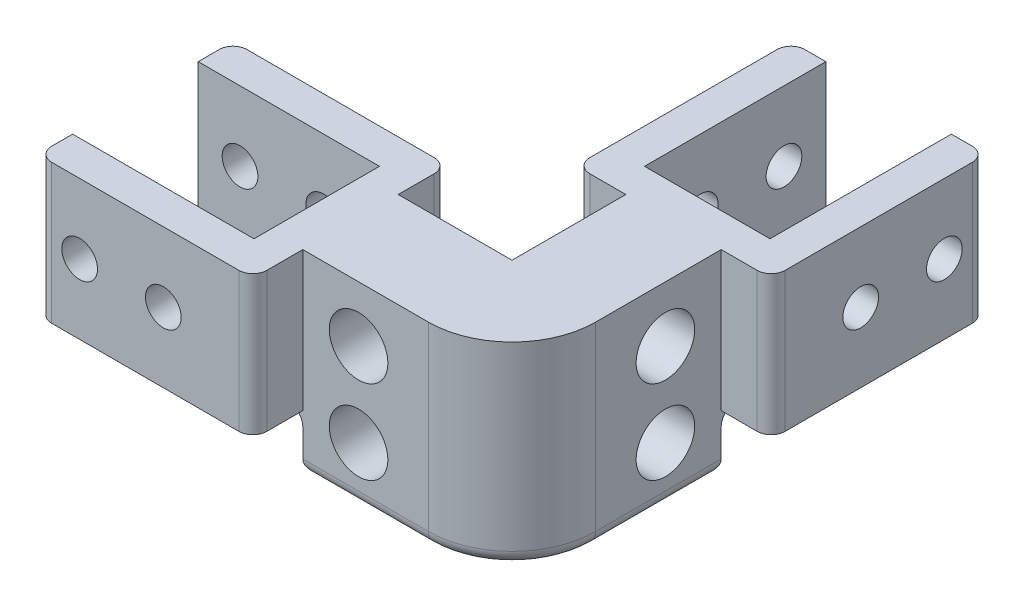
SolidWorks part; units mm, degrees
ref_plane "정면" through (0, 0, 0) normal (0, 0, 1) x (1, 0, 0)
ref_plane "윗면" through (0, 0, 0) normal (0, 1, 0) x (1, 0, 0)
ref_plane "우측면" through (0, 0, 0) normal (1, 0, 0) x (0, 0, -1)
sketch "스케치1" plane through (0, 0, 0) normal (0, 1, 0) x (1, 0, 0)
  line L0 (-17.5, 67.5) -> (-11.25, 67.5)
  line L1 (-11.25, 67.5) -> (-11.25, 37.5)
  line L2 (-11.25, 37.5) -> (11.25, 37.5)
  line L3 (11.25, 37.5) -> (11.25, 67.5)
  line L4 (11.25, 67.5) -> (17.5, 67.5)
  line L5 (17.5, 67.5) -> (17.5, -17.5)
  line L6 (17.5, -17.5) -> (-67.5, -17.5)
  line L7 (-67.5, -17.5) -> (-67.5, -11.25)
  line L8 (-67.5, -11.25) -> (-37.5, -11.25)
  line L9 (-37.5, -11.25) -> (-37.5, 11.25)
  line L10 (-37.5, 11.25) -> (-67.5, 11.25)
  line L11 (-67.5, 11.25) -> (-67.5, 17.5)
  line L12 (-67.5, 17.5) -> (-17.5, 17.5)
  line L13 (-17.5, 17.5) -> (-17.5, 67.5)
  point P14 (0, 37.5)
  point P18 (-37.5, 0)
  point P21 (-67.5, -14.375)
  dimension "D1" = 22.5
  dimension "D2" = 22.5
  dimension "D3" = 35
  dimension "D4" = 35
  dimension "D5" = 30
  dimension "D6" = 30
  dimension "D7" = 37.5
  dimension "D8" = 37.5
extrude "보스-돌출1" add sketch "스케치1" along normal blind 25
sketch "스케치2" plane through (17.5, 0, 0) normal (1, 0, 0) x (0, 0, -1)
  line L0 (67.5, 25) -> (67.5, 0) construction
  line L1 (-17.5, 25) -> (67.5, 25) construction
  circle A0 centre (60, 12.5) radius 3.2
  circle A1 centre (45, 12.5) radius 3.2
  dimension "D3" = 6.4
  dimension "D1" = 15
  dimension "D2" = 7.5
  dimension "D4" = 12.5
extrude "컷-돌출1" cut sketch "스케치2" against normal up to surface (35 mm away) up to face at (-17.5, 12.5, -42.5)
sketch "스케치3" plane through (0, 0, 17.5) normal (0, 0, 1) x (1, 0, 0)
  line L0 (-67.5, 25) -> (-67.5, 0) construction
  line L1 (-67.5, 25) -> (17.5, 25) construction
  circle A0 centre (-60, 12.5) radius 3.2
  circle A1 centre (-45, 12.5) radius 3.2
  dimension "D2" = 6.4
  dimension "D1" = 15
  dimension "D3" = 7.5
  dimension "D4" = 12.5
extrude "컷-돌출2" cut sketch "스케치3" against normal up to surface (35 mm away) up to face at (-42.5, 12.5, -17.5)
sketch "스케치14" plane through (0, 25, 0) normal (0, 1, 0) x (1, 0, 0)
  line L1 (-11.25, 37.5) -> (11.25, 37.5)
  line L2 (-11.25, 37.5) -> (-11.25, 35)
  line L3 (-11.25, 35) -> (11.25, 35)
  line L4 (11.25, 37.5) -> (11.25, 35)
  line L5 (-37.5, 11.25) -> (-35, 11.25)
  line L6 (-37.5, 11.25) -> (-37.5, -11.25)
  line L7 (-37.5, -11.25) -> (-35, -11.25)
  line L8 (-35, 11.25) -> (-35, -11.25)
  dimension "D1" = 2.5
  dimension "D2" = 2.5
extrude "컷-돌출12" cut sketch "스케치14" against normal up to surface (25 mm away) up to face at (-24.6429, 0, -24.6429)
sketch "스케치5" plane through (0, 25, 0) normal (0, 1, 0) x (1, 0, 0)
  line L0 (-17.5, 67.5) -> (-17.5, 17.5) construction
  line L1 (-8.55, 8.55) -> (-28.95, 8.55)
  line L2 (-8.55, 8.55) -> (-8.55, 28.95)
  line L3 (-8.55, 28.95) -> (-28.95, 28.95)
  line L4 (-28.95, 8.55) -> (-28.95, 28.95)
  line L5 (-17.5, 17.5) -> (-67.5, 17.5) construction
  line L6 (-28.95, -8.55) -> (-28.95, -17.5)
  line L7 (-67.5, -17.5) -> (17.5, -17.5) construction
  line L8 (-28.95, -17.5) -> (17.5, -17.5)
  line L9 (17.5, -17.5) -> (17.5, 28.95)
  line L10 (17.5, -17.5) -> (17.5, 67.5) construction
  line L11 (17.5, 28.95) -> (8.55, 28.95)
  line L12 (8.55, 28.95) -> (8.55, -8.55)
  line L13 (8.55, -8.55) -> (-28.95, -8.55)
  dimension "D1" = 20.4
  dimension "D2" = 20.4
  dimension "D3" = 8.95
  dimension "D4" = 8.95
  dimension "D5" = 8.95
  dimension "D6" = 8.95
extrude "컷-돌출7" cut sketch "스케치5" against normal up to surface (25 mm away) up to face at (-24.2857, 0, -24.2857)
sketch "스케치15" plane through (0, 0, 0) normal (0, -1, 0) x (1, 0, 0)
  line L0 (8.55, 8.55) -> (8.55, -28.95)
  line L1 (8.55, -28.95) -> (-8.55, -28.95)
  line L2 (-8.55, -28.95) -> (-8.55, -8.55)
  line L3 (-8.55, -8.55) -> (-28.95, -8.55)
  line L4 (-28.95, -8.55) -> (-28.95, 8.55)
  line L5 (8.55, 8.55) -> (-28.95, 8.55) construction
  line L6 (-28.95, 8.55) -> (-28.95, 17.5) construction
  line L7 (-28.95, 8.55) -> (8.55, 8.55)
extrude "보스-돌출2" add sketch "스케치15" along normal blind 10
sketch "스케치10" plane through (0, 0, 8.55) normal (0, 0, 1) x (1, 0, 0)
  line L0 (-28.95, 0) -> (-28.95, 25) construction
  line L2 (8.55, 25) -> (-28.95, 25) construction
  circle A0 centre (-18.95, 15) radius 3.2
  circle A1 centre (-18.95, 0) radius 3.2
  point P8 (0, 0)
  dimension "D2" = 6.4
  dimension "D1" = 10
  dimension "D3" = 10
  dimension "D4" = 15
extrude "컷-돌출8" cut sketch "스케치10" against normal up to surface (17.1 mm away) up to face at (-20.79, 6, -8.55)
sketch "스케치11" plane through (0, 0, 8.55) normal (0, 0, 1) x (1, 0, 0)
  circle A0 centre (-18.95, 15) radius 5.25
  circle A1 centre (-18.95, 15) radius 3.2 construction
  circle A2 centre (-18.95, 0) radius 5.25
  point P7 (0, 0)
  dimension "D1" = 10.5
extrude "컷-돌출9" cut sketch "스케치11" against normal offset from surface (12.1 mm away) 5 up to face at (-15.75, 0, -8.55)
sketch "스케치12" plane through (8.55, 0, 0) normal (1, 0, 0) x (0, 0, -1)
  line L0 (28.95, 0) -> (28.95, 25) construction
  line L1 (28.95, 25) -> (67.5, 25) construction
  circle A0 centre (18.95, 15) radius 3.2
  circle A1 centre (18.95, 0) radius 3.2
  point P8 (0, 0)
  dimension "D3" = 6.4
  dimension "D1" = 10
  dimension "D2" = 10
  dimension "D4" = 15
extrude "컷-돌출10" cut sketch "스케치12" against normal up to surface (17.1 mm away) up to face at (-8.55, 6, -20.79)
sketch "스케치13" plane through (8.55, 0, 0) normal (1, 0, 0) x (0, 0, -1)
  circle A0 centre (18.95, 15) radius 5.25
  circle A1 centre (18.95, 0) radius 5.25
  dimension "D1" = 10.5
extrude "컷-돌출11" cut sketch "스케치13" against normal offset from surface (12.1 mm away) 5 up to face at (-8.55, 0, -22.15)
fillet "필렛2" radius 2.5 12 edges at (-67.5, 12.5, 17.5) (-67.5, 12.5, -17.5) (-17.5, 12.5, -67.5) (17.5, 12.5, -67.5) (17.5, 12.5, -28.95) (-17.5, 12.5, -28.95) (-28.95, 12.5, -17.5) (-28.95, 12.5, 17.5) (-10.2, -10, 8.55) (8.55, -10, -10.2) (-28.95, -10, 0) (0, -10, -28.95)
fillet "필렛3" radius 15 2 edges at (8.55, 8.75, 8.55) (7.8178, -9.2678, 7.8178)
fillet "필렛5" radius 2.5 2 edges at (-28.95, 0, 0) (0, 0, -28.95)
